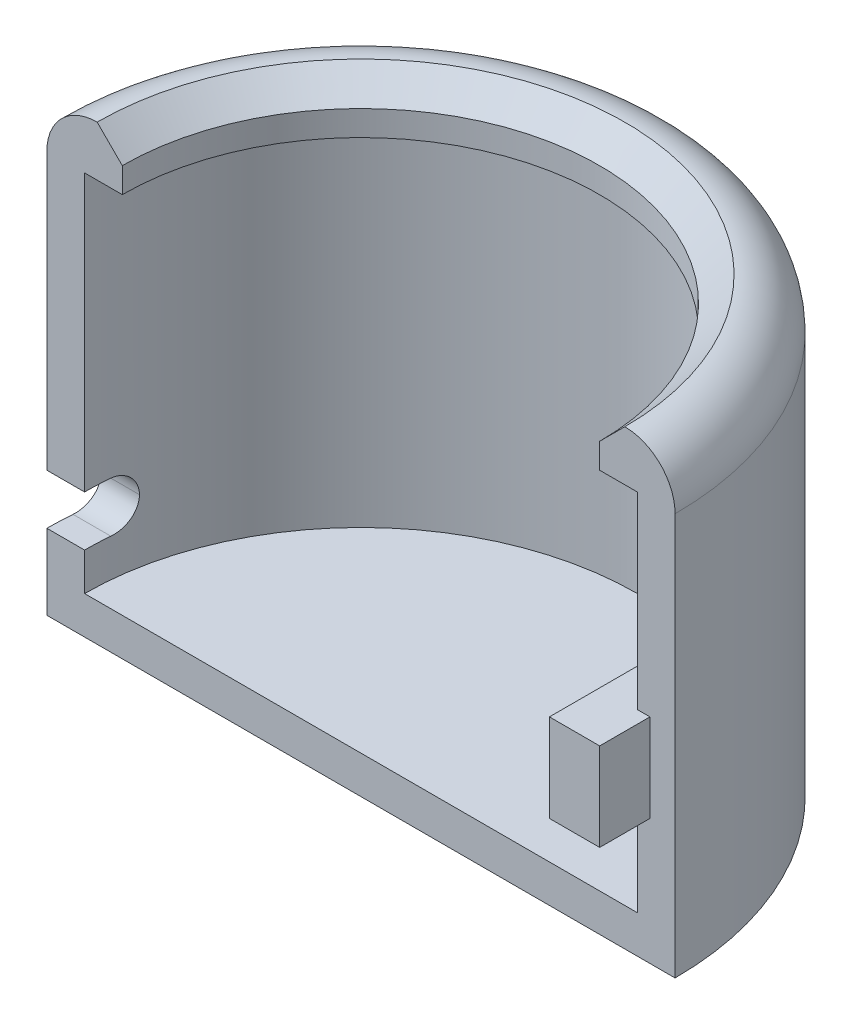
SolidWorks part; units mm, degrees
ref_plane "Plan de face" through (0, 0, 0) normal (0, 0, 1) x (1, 0, 0)
ref_plane "Plan de dessus" through (0, 0, 0) normal (0, 1, 0) x (1, 0, 0)
ref_plane "Plan de droite" through (0, 0, 0) normal (1, 0, 0) x (0, 0, -1)
sketch "Esquisse3" plane through (0, 0, 0) normal (0, 0, 1) x (1, 0, 0)
  line L0 (0, 0) -> (12.5, 0)
  line L1 (12.5, 0) -> (12.5, 18)
  line L2 (12.5, 18) -> (9.5, 18)
  line L3 (9.5, 18) -> (9.5, 16)
  line L4 (9.5, 16) -> (11, 16)
  line L5 (11, 16) -> (11, 1.5)
  line L6 (11, 1.5) -> (0, 1.5)
  line L7 (0, 1.5) -> (0, 0)
  line L8 (0, 0) -> (0, 28.6696) construction
  point P3 (9.5, 19.1495)
  point P11 (9.5, 17.9629)
  dimension "D1" = 19
  dimension "D2" = 25
  dimension "D3" = 14.5
  dimension "D4" = 2
  dimension "D5" = 1.5
  dimension "D6" = 22
revolve "Révolution1" add sketch "Esquisse3" angle 180 about L8
chamfer "Chanfrein1" distance 1 angle 45 1 edges at (0, 18, -9.5)
fillet "Congé1" radius 2 1 edges at (0, 18, -12.5)
sketch "Esquisse4" plane through (0, 0, 0) normal (1, 0, 0) x (0, 0, -1)
  line L0 (0, 0) -> (0, 3) construction
  line L1 (-2, 3) -> (2, 3)
  line L2 (-2, 3) -> (-2, 5)
  line L3 (-2, 5) -> (2, 5)
  line L4 (2, 3) -> (2, 5)
  dimension "D1" = 4
  dimension "D2" = 2
  dimension "D3" = 1.5
extrude "Enlèv. mat.-Extru.1" cut sketch "Esquisse4" against normal up to next
fillet "Congé2" radius 1 2 edges at (-11.5778, 5, -2) (-11.5778, 3, -2)
sketch "Esquisse5" plane through (0, 0, 0) normal (0, 0, 1) x (1, 0, 0)
  line L0 (11, 16) -> (11, 1.5) construction
  line L1 (9.5, 8.5) -> (11.5, 8.5)
  line L2 (9.5, 8.5) -> (9.5, 5)
  line L3 (9.5, 5) -> (11.5, 5)
  line L4 (11.5, 8.5) -> (11.5, 5)
  dimension "D1" = 3.5
  dimension "D2" = 2
  dimension "D3" = 1.5
  dimension "D4" = 3.5
extrude "Boss.-Extru.2" add sketch "Esquisse5" against normal up to surface and the other way blind 2 up to face at (-6.0789, 6.129, -2.9349)
